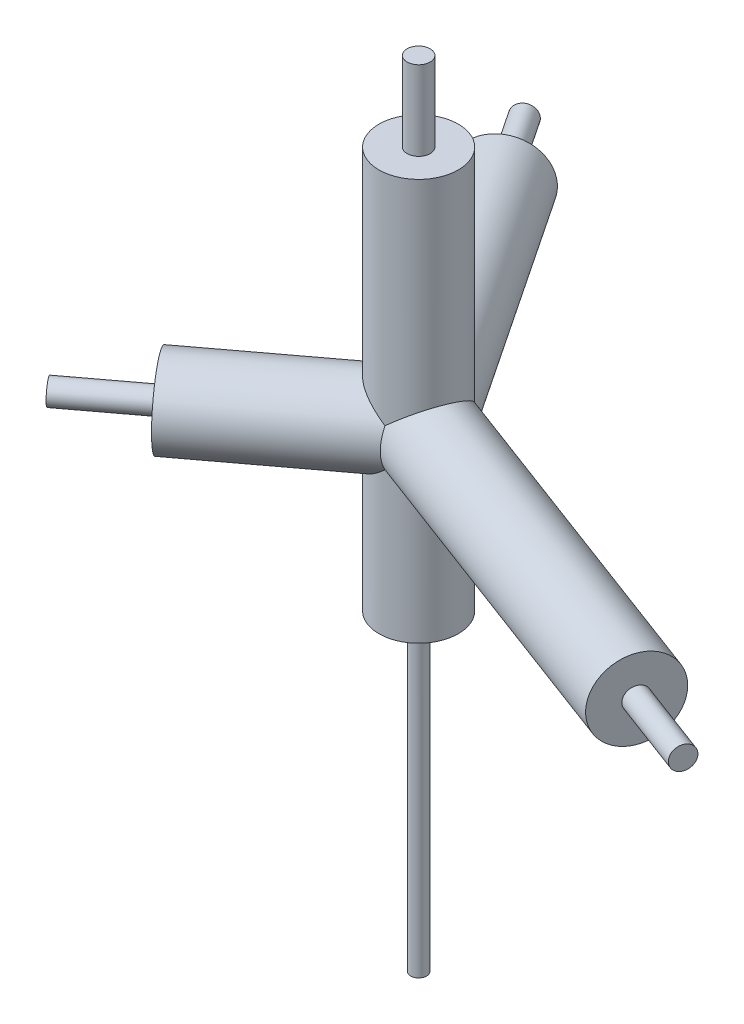
SolidWorks part; units mm, degrees
ref_plane "前视基准面" through (0, 0, 0) normal (0, 0, 1) x (1, 0, 0)
ref_plane "上视基准面" through (0, 0, 0) normal (0, 1, 0) x (1, 0, 0)
ref_plane "右视基准面" through (0, 0, 0) normal (1, 0, 0) x (0, 0, -1)
sketch "草图1" plane through (0, 0, 0) normal (0, 1, 0) x (1, 0, 0)
  line L0 (-26.6667, 40) -> (-26.6667, -20) construction
  line L1 (-26.6667, -20) -> (53.3333, -20) construction
  line L2 (-26.6667, 40) -> (53.3333, -20) construction
  line L3 (0, 0) -> (-26.6667, 40)
  line L4 (0, 0) -> (-26.6667, -20)
  line L5 (0, 0) -> (53.3333, -20)
  line L6 (0, 0) -> (41602.5147, 27735.0098) construction
  line L7 (0, 0) -> (30000, -40000) construction
  line L8 (0, 0) -> (17556.1721, 46816.4589) construction
  dimension "D1" = 60
  dimension "D2" = 80
  dimension "D3" = 20
  dimension "D4" = 26.6667
  dimension "D5" = 90
  dimension "D6" = 90
  dimension "D7" = 90
ref_plane "基准面1" through (0, 0, 0) normal (-0.8, 0, 0.6) x (0.6, 0, 0.8)
sketch "草图2" plane through (0, 0, 0) normal (-0.8, 0, 0.6) x (0.6, 0, 0.8)
  circle A0 centre (0, 0) radius 5
  dimension "D1" = 10
ref_plane "基准面2" through (0, 0, 0) normal (0.9363, 0, 0.3511) x (0.3511, 0, -0.9363)
ref_plane "基准面3" through (0, 0, 0) normal (0.5547, 0, 0.8321) x (0.8321, 0, -0.5547)
sketch "草图3" plane through (0, 0, 0) normal (0.9363, 0, 0.3511) x (0.3511, 0, -0.9363)
  circle A0 centre (0, 0) radius 5
  dimension "D1" = 10
sketch "草图4" plane through (0, 0, 0) normal (0.5547, 0, 0.8321) x (0.8321, 0, -0.5547)
  circle A0 centre (0, 0) radius 5
  dimension "D1" = 10
sweep "扫描1" add profiles "草图3" path "草图1"
sketch "草图5" plane through (0, 0, 0) normal (0, 1, 0) x (1, 0, 0)
  line L0 (0, 0) -> (-26.6667, 40)
sweep "扫描7" add profiles "草图4" path "草图5"
sketch "草图6" plane through (0, 0, 0) normal (0, 1, 0) x (1, 0, 0)
  line L0 (0, 0) -> (-26.6667, -20)
sweep "扫描8" add profiles "草图2" path "草图6"
sketch "草图7" plane through (-26.6667, 0, -40) normal (-0.5547, 0, -0.8321) x (-0.8321, 0, 0.5547)
  circle A0 centre (0, 0) radius 5
  circle A1 centre (0, 0) radius 1.45
  dimension "D1" = 10
  dimension "D2" = 2.9
extrude "切除-拉伸1" cut sketch "草图7" against normal blind 10
sketch "草图8" plane through (-26.6667, 0, 20) normal (-0.8, 0, 0.6) x (0.6, 0, 0.8)
  circle A0 centre (0, 0) radius 5
  circle A1 centre (0, 0) radius 1.45
  dimension "D1" = 10
  dimension "D2" = 2.9
extrude "切除-拉伸2" cut sketch "草图8" against normal blind 10
sketch "草图9" plane through (53.3333, 0, 20) normal (0.9363, 0, 0.3511) x (0.3511, 0, -0.9363)
  circle A0 centre (0, 0) radius 5
  circle A1 centre (0, 0) radius 1.45
  dimension "D1" = 10
  dimension "D2" = 2.9
extrude "切除-拉伸3" cut sketch "草图9" against normal blind 10
sketch "草图10" plane through (0, 0, 0) normal (0, 1, 0) x (1, 0, 0)
  circle A0 centre (0, 0) radius 5
  dimension "D1" = 10
extrude "凸台-拉伸1" add sketch "草图10" along normal blind 40 and the other way blind 60
sketch "草图12" plane through (0, 40, 0) normal (0, 1, 0) x (1, 0, 0)
  circle A0 centre (0, 0) radius 5
  circle A1 centre (0, 0) radius 1.45
  dimension "D1" = 10
  dimension "D2" = 2.9
extrude "切除-拉伸5" cut sketch "草图12" against normal blind 10
sketch "草图13" plane through (0, 0, 0) normal (1, 0, 0) x (0, 0, -1)
  line L0 (0, -1000) -> (0, 49000) construction
  line L1 (-5, -60) -> (5, -60) construction
  line L2 (-1, -20.025) -> (-1, -59.975)
  line L4 (-5, -60) -> (-1, -60)
  line L5 (-5, -60) -> (-5, -59.0176)
  line L6 (-5, -59.0176) -> (-1, -59.0176)
  line L7 (-1, -60) -> (-1, -59.0176)
  circle A0 centre (0, -40) radius 20
  dimension "D2" = 40
  dimension "D1" = 20
  dimension "D3" = 1
revolve "切除-旋转1" cut sketch "草图13" angle 360 about L0 region at (0, -39.9044, 9.0623) region at (0, -59.8085, 3.778)
